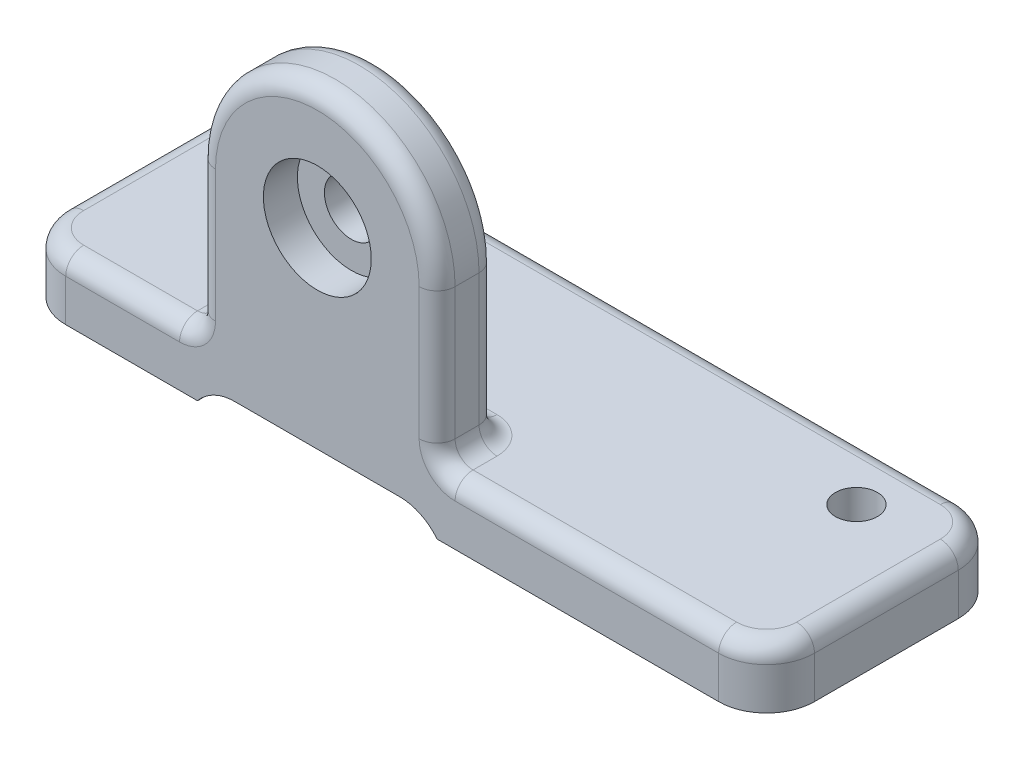
SolidWorks part; units mm, degrees
ref_plane "Front Plane" through (0, 0, 0) normal (0, 0, 1) x (1, 0, 0)
ref_plane "Top Plane" through (0, 0, 0) normal (0, 1, 0) x (1, 0, 0)
ref_plane "Right Plane" through (0, 0, 0) normal (1, 0, 0) x (0, 0, -1)
sketch "Sketch2" plane through (0, 0, 0) normal (0, 1, 0) x (1, 0, 0)
  line L1 (0, 0) -> (125, 0)
  line L2 (0, 0) -> (0, 40)
  line L3 (0, 40) -> (125, 40)
  line L4 (125, 0) -> (125, 40)
  dimension "D1" = 125
  dimension "D2" = 40
extrude "Base Plate" add sketch "Sketch2" along normal blind 10
sketch "Sketch3" plane through (0, 0, 0) normal (0, 0, 1) x (1, 0, 0)
  line L0 (30, 0) -> (30, 35)
  line L1 (0, 0) -> (125, 0) construction
  line L2 (70, 35) -> (70, 0)
  line L3 (0, 10) -> (0, 0) construction
  line L4 (30, 0) -> (70, 0)
  arc A0 (30, 35) -> (70, 35) centre (50, 35) cw
  point P9 (0, 5)
  dimension "D3" = 20
  dimension "D1" = 35
  dimension "D2" = 50
extrude "VertBoss" add sketch "Sketch3" against normal blind 10
ref_plane "Plane1" through (0, 0, 0) normal (1, 0, 0) x (0, 0, -1)
sketch "Sketch5" plane through (0, 0, 0) normal (0, 0, 1) x (1, 0, 0)
  line L0 (0, 0) -> (125, 0) construction
  line L1 (30, 0) -> (70, 0)
  line L2 (30, 0) -> (30, 3)
  line L3 (30, 3) -> (70, 3)
  line L4 (70, 0) -> (70, 3)
  line L5 (30, 35) -> (30, 10) construction
  line L6 (70, 10) -> (70, 35) construction
  point P6 (0, 0)
  point P9 (0, 0)
  dimension "D1" = 3
extrude "BottomSlot" cut sketch "Sketch5" against normal through all
hole_wizard "CBORE for M8 Hex Head Bolt1" positions "Sketch6" profile "Sketch7" counterbore size "M8" standard "ANSI Metric" end condition through all
sketch "Sketch6" plane through (0, 0, 0) normal (0, 0, 1) x (1, 0, 0)
  point P0 (50, 35)
sketch "Sketch7" plane through (50, 35, 0) normal (1, 0, 0) x (0, -1, 0)
  line L0 (0, 0) -> (0, 40)
  line L1 (0, 40) -> (4.5, 40)
  line L3 (4.5, 40) -> (4.5, 5.68)
  line L4 (4.5, 5.68) -> (9.005, 5.68)
  line L5 (9.005, 5.68) -> (9.005, 0)
  line L7 (9.005, 0) -> (0, 0)
  line L11 (0, -6.35) -> (0, 107.95) construction
  dimension "Thru Hole Dia." = 9
  dimension "Thru Hole Depth" = 40
  dimension "C'Bore Dia." = 18.01
  dimension "C'Bore Depth" = 5.68
hole_wizard "Ø7.0 (7) Diameter Hole1" positions "Sketch8" profile "Sketch9" hole size "Ø7.0" standard "ANSI Metric" end condition through all
sketch "Sketch8" plane through (0, 10, 0) normal (0, 1, 0) x (1, 0, 0)
  line L0 (0, 40) -> (0, 0) construction
  line L1 (125, 40) -> (0, 40) construction
  line L2 (125, 0) -> (125, 40) construction
  point P0 (15, 30)
  point P2 (110, 30)
  dimension "D1" = 15
  dimension "D2" = 10
  dimension "D3" = 15
  dimension "D4" = 10
sketch "Sketch9" plane through (15, 10, -30) normal (1, 0, 0) x (0, 0, 1)
  line L0 (0, 0) -> (0, 10)
  line L1 (0, 10) -> (3.5, 10)
  line L2 (3.5, 10) -> (3.5, 0)
  line L5 (3.5, 0) -> (0, 0)
  line L11 (0, -6.35) -> (0, 107.95) construction
  dimension "Thru Hole Dia." = 7
  dimension "Thru Hole Depth" = 10
fillet "Fillet1" radius 8 6 edges at (0, 5, -40) (125, 5, -40) (0, 5, 0) (125, 5, 0) (70, 3, -20) (30, 3, -20)
fillet "Fillet2" radius 3 18 edges at (70, 22.5, -10) (30, 22.5, -10) (70, 22.5, 0) (30, 22.5, 0) (50, 55, -10) (50, 55, 0) (122.6569, 10, -37.6569) (125, 10, -20) (62.5, 10, -40) (122.6569, 10, -2.3431) (2.3431, 10, -37.6569) (93.5, 10, 0) (0, 10, -20) (70, 10, -5) (2.3431, 10, -2.3431) (50, 10, -10) (19, 10, 0) (30, 10, -5)
